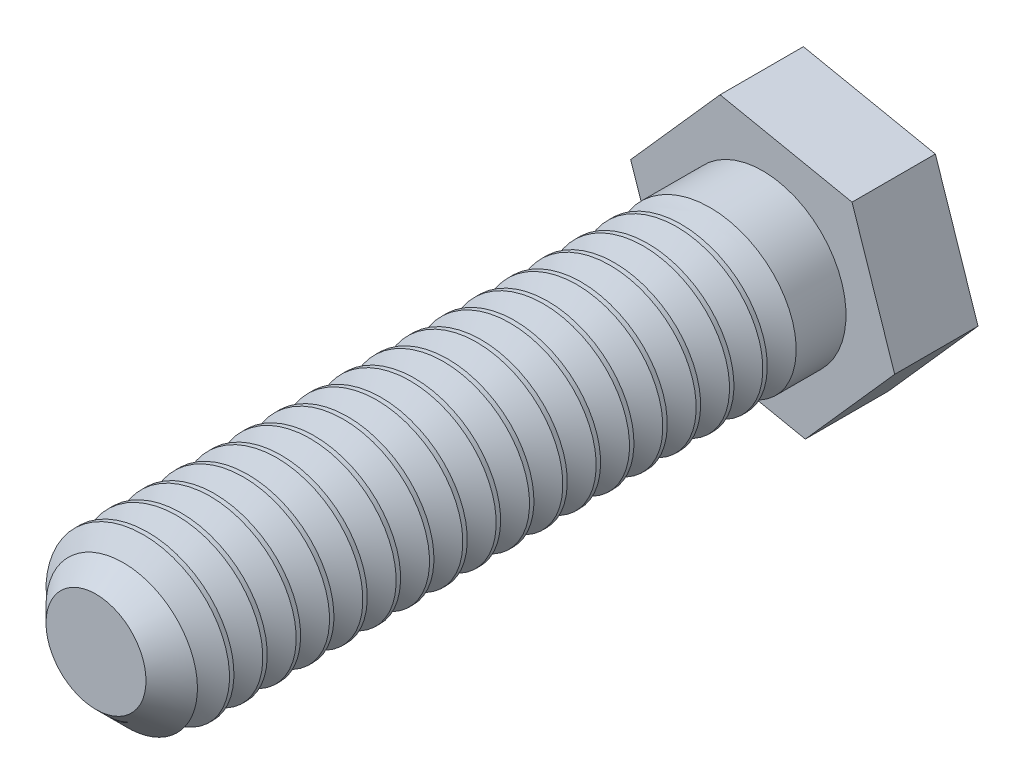
SolidWorks part; units mm, degrees
ref_plane "Front Plane" through (0, 0, 0) normal (0, 0, 1) x (1, 0, 0)
ref_plane "Top Plane" through (0, 0, 0) normal (0, 1, 0) x (1, 0, 0)
ref_plane "Right Plane" through (0, 0, 0) normal (1, 0, 0) x (0, 0, -1)
sketch "Sketch1" plane through (0, 0, 0) normal (0, 0, 1) x (1, 0, 0)
  circle A0 centre (0, 0) radius 5
  dimension "D1" = 10
extrude "Boss-Extrude1" add sketch "Sketch1" along normal blind 40
chamfer "Chamfer1" distance 2 angle 45 1 edges at (5, 0, 40)
sketch "Sketch2" plane through (0, 0, 40) normal (0, 0, 1) x (1, 0, 0)
  circle A0 centre (0, 0) radius 5 construction
  circle A1 centre (0, 0) radius 5
curve "Helix/Spiral1" pitch 2 height 38 radius 5 centre (0, 0, 40) axis (0, 0, -1) start towards (-1, 0, 0)
ref_plane "Plane1" through (-5, 0, 40) normal (0, 0.998, -0.0635) x (1, 0, 0)
sketch "Sketch4" plane through (-5, 0, 40) normal (0, 0.998, -0.0635) x (1, 0, 0)
  line L0 (0, -0.866) -> (1.5, -0.866) construction
  line L1 (1.5, -0.866) -> (0, 0)
  line L2 (0, 0) -> (0, -1.7321)
  line L3 (0, -1.7321) -> (1.5, -0.866)
  circle A0 centre (0.5, -0.866) radius 0.5 construction
  dimension "D1" = 1
sweep "Cut-Sweep1" cut profiles "Sketch4" path "Helix/Spiral1"
sketch "Sketch5" plane through (0, 0, 0) normal (0, 0, -1) x (-1, 0, 0)
  line L1 (-2.5576, -7.6676) -> (5.3616, -6.0487)
  line L2 (5.3616, -6.0487) -> (7.9191, 1.6189)
  line L3 (7.9191, 1.6189) -> (2.5576, 7.6676)
  line L4 (2.5576, 7.6676) -> (-5.3616, 6.0487)
  line L5 (-5.3616, 6.0487) -> (-7.9191, -1.6189)
  line L6 (-7.9191, -1.6189) -> (-2.5576, -7.6676)
  circle A0 centre (0, 0) radius 7 construction
  circle A1 centre (0, 0) radius 5 construction
  dimension "D1" = 14
extrude "Boss-Extrude2" add sketch "Sketch5" along normal blind 5
